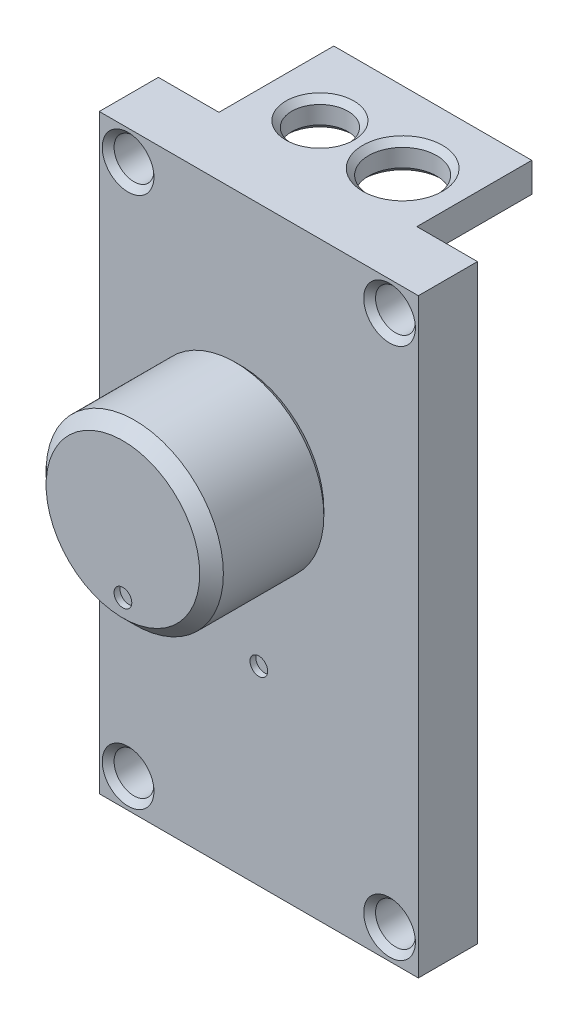
SolidWorks part; units mm, degrees
ref_plane "Front" through (0, 0, 0) normal (0, 0, 1) x (1, 0, 0)
ref_plane "Top" through (0, 0, 0) normal (0, 1, 0) x (1, 0, 0)
ref_plane "Right" through (0, 0, 0) normal (1, 0, 0) x (0, 0, -1)
sketch "Sketch1" plane through (0, 0, 0) normal (0, 0, 1) x (1, 0, 0)
  line L0 (-3.9725, 10.7262) -> (0.1506, 10.7262)
  line L1 (-5.9109, 4.6646) -> (-5.9109, 8.7877)
  line L2 (2.0891, 4.6646) -> (2.0891, 8.7877)
  line L3 (-3.9725, 2.7262) -> (0.1506, 2.7262)
  line L5 (-1.9109, 10.7262) -> (-1.9109, 2.7262) construction
  line L6 (25.0891, 42.9762) -> (25.0891, -57.0238) construction
  line L8 (25.0891, -57.0238) -> (-28.9109, -57.0238) construction
  line L9 (25.0891, 42.9762) -> (25.0891, -57.0238)
  line L10 (25.0891, 42.9762) -> (-28.9109, 42.9762)
  line L11 (25.0891, -57.0238) -> (-28.9109, -57.0238)
  line L12 (-28.9109, 42.9762) -> (-28.9109, -57.0238)
  line L13 (-19.1609, 6.7262) -> (15.3391, 6.7262) construction
  line L14 (-19.1609, 42.9762) -> (-19.1609, -29.5238) construction
  line L15 (15.3391, 42.9762) -> (15.3391, -29.5238) construction
  arc A0 (-3.9725, 10.7262) -> (-5.9109, 8.7877) centre (-1.9109, 6.7262) ccw
  arc A1 (2.0891, 8.7877) -> (0.1506, 10.7262) centre (-1.9109, 6.7262) ccw
  arc A3 (0.1506, 2.7262) -> (2.0891, 4.6646) centre (-1.9109, 6.7262) ccw
  arc A4 (-5.9109, 4.6646) -> (-3.9725, 2.7262) centre (-1.9109, 6.7262) ccw
  dimension "D1" = 9
  dimension "D3" = 8
  dimension "D4" = 8
extrude "Boss-Extrude1" add sketch "Sketch1" along normal blind 10
ref_plane "Plane1" through (0, 0, 13) normal (0, 0, 1) x (1, 0, 0)
sketch "Sketch2" plane through (0, 0, 13) normal (0, 0, 1) x (1, 0, 0)
  line L0 (0.9157, 8.2262) -> (-4.7376, 8.2262)
  arc A0 (-4.7376, 8.2262) -> (0.9157, 8.2262) centre (-1.9109, 6.7262) ccw
  circle A1 centre (-1.9109, 6.7262) radius 15
  point P1 (-1.9109, 3.5262)
  dimension "D1" = 3.2
  dimension "D3" = 30
  dimension "D2" = 4.7
extrude "Boss-Extrude2" add sketch "Sketch2" along normal blind 20 separate body contours A1
extrude "Cut-Extrude1" cut sketch "Sketch2<3>" along normal blind 11 contours L0 A0
sketch "Sketch2<3>" plane through (0, 0, 13) normal (0, 0, 1) x (1, 0, 0) same geometry as "Sketch2"
chamfer "Chamfer1" distance 2 angle 45 1 edges at (13.0891, 6.7262, 33)
sketch "Sketch5" plane through (0, 0, 33) normal (0, 0, 1) x (1, 0, 0)
  line L0 (-1.9109, 6.7262) -> (-1.9109, -3.2738) construction
  circle A1 centre (-1.9109, -3.2738) radius 1.5
  dimension "D1" = 3
  dimension "D2" = 10
extrude "Cut-Extrude2" cut sketch "Sketch5" against normal blind 1 contours A1
chamfer "Chamfer2" distance 1 angle 45 3 edges at (-1.9109, 3.5262, 13) (-1.9109, 8.2262, 13) (13.0891, 6.7262, 13)
sketch "Sketch6" plane through (0, 0, 13) normal (0, 0, -1) x (-1, 0, 0)
  line L0 (-1.464, 9.2262) -> (5.2858, 9.2262) construction
  line L1 (-1.464, 9.2262) -> (5.2858, 9.2262) construction
  line L2 (-1.7071, 9.7262) -> (5.5289, 9.7262)
  circle A0 centre (1.9109, 6.7262) radius 14 construction
  arc A1 (-1.464, 9.2262) -> (5.2858, 9.2262) centre (1.9109, 6.7262) ccw construction
  circle A2 centre (1.9109, 6.7262) radius 14 construction
  arc A3 (-1.464, 9.2262) -> (5.2858, 9.2262) centre (1.9109, 6.7262) ccw construction
  arc A4 (-1.7071, 9.7262) -> (5.5289, 9.7262) centre (1.9109, 6.7262) ccw
  circle A5 centre (1.9109, 6.7262) radius 12.5
  dimension "D1" = 0.5
  dimension "D2" = 1.5
extrude "Cut-Extrude3" cut sketch "Sketch6" against normal blind 15.5
fillet "Fillet1" radius 1 3 edges at (-14.4109, 6.7262, 28.5) (-1.9109, 2.0262, 28.5) (-1.9109, 9.7262, 28.5)
sketch "Sketch7" plane through (0, 0, 10) normal (0, 0, 1) x (1, 0, 0)
  line L0 (-1.9109, -24.8226) -> (-1.9109, 6.7262) construction
  circle A0 centre (-1.9109, -24.8226) radius 1.5
  circle A1 centre (-1.9109, -3.2738) radius 1.5 construction
extrude "Cut-Extrude4" cut sketch "Sketch7" against normal blind 1
sketch "Sketch8" plane through (0, 42.9762, 0) normal (0, 1, 0) x (1, 0, 0)
  line L0 (15.3391, 19.938) -> (-19.1609, 19.938) construction
  line L1 (15.3391, 19.938) -> (15.3391, 0) construction
  line L2 (-19.1609, 19.938) -> (-19.1609, 0) construction
  line L3 (-18.6609, 0.5) -> (-18.6609, 0)
  line L4 (25.0891, 0) -> (-28.9109, 0) construction
  line L5 (14.8391, 19.438) -> (14.8391, 0.5)
  line L6 (-18.6609, 0) -> (14.8391, 0)
  line L7 (-18.6609, 19.438) -> (-18.6609, 0.5)
  line L8 (14.8391, 19.438) -> (-18.6609, 19.438)
  line L9 (14.8391, 0.5) -> (-18.6609, 0.5) construction
  line L10 (15.3391, 0) -> (-19.1609, 0) construction
  line L11 (14.8391, 0) -> (14.8391, 0.5)
  dimension "D1" = 0.5
extrude "Boss-Extrude3" add sketch "Sketch8" against normal blind 5
hole_wizard "CBORE for #4 Binding Head Machine Screw1" positions "Sketch10" profile "Sketch9" counterbore size "#4" standard "ANSI Inch" end condition through all
sketch "Sketch10" plane through (0, 0, 10) normal (0, 0, 1) x (1, 0, 0)
  point P0 (20.2141, -52.0238)
  point P3 (-24.0359, -52.0238)
  point P6 (-24.0359, 37.9762)
  point P9 (20.2141, 37.9762)
sketch "Sketch9" plane through (20.2141, -52.0238, 10) normal (1, 0, 0) x (0, -1, 0)
  line L0 (0, 0) -> (0, 29.438)
  line L1 (0, 29.438) -> (1.6319, 29.438)
  line L3 (1.6319, 29.438) -> (1.632, 7.7272)
  line L4 (1.632, 7.7272) -> (3.3731, 7.7272)
  line L5 (3.3731, 7.7272) -> (3.3731, 0)
  line L7 (3.3731, 0) -> (0, 0)
  line L11 (0, -6.35) -> (0, 107.95) construction
  dimension "Thru Hole Dia." = 3.2639
  dimension "Thru Hole Depth" = 29.438
  dimension "C'Bore Dia." = 6.7462
  dimension "C'Bore Depth" = 7.7272
sketch "Sketch11" plane through (0, 42.9762, 0) normal (0, 1, 0) x (1, 0, 0)
  line L0 (-8.9109, 7.339) -> (5.0891, 7.339) construction
  line L1 (14.8391, 19.438) -> (-18.6609, 19.438) construction
  line L3 (-1.9109, -4.7599) -> (-1.9109, 19.438) construction
  circle A0 centre (5.0891, 7.339) radius 5.75
  circle A1 centre (-8.9109, 7.339) radius 4.75
  point P5 (-1.9109, 7.339)
  dimension "D1" = 9.5
  dimension "D2" = 11.5
  dimension "D3" = 14
extrude "Cut-Extrude5" cut sketch "Sketch11" against normal up to next (5 mm away) contours A1 | A0
chamfer "Chamfer4" distance 1 angle 45 4 edges at (-13.6609, 37.9762, -7.339) (-13.6609, 42.9762, -7.339) (-0.6609, 37.9762, -7.339) (-0.6609, 42.9762, -7.339)
sketch "Sketch12" plane through (0, 0, 0) normal (0, 0, -1) x (-1, 0, 0)
  line L10 (-16.0891, 28.9762) -> (-16.0891, 34.9762)
  line L11 (-16.0891, 34.9762) -> (19.9109, 34.9762)
  line L12 (19.9109, 34.9762) -> (19.9109, 28.9762)
  line L13 (18.6609, 37.9762) -> (-14.8391, 37.9762) construction
  line L20 (19.9109, 28.9762) -> (-16.0891, 28.9762)
  line L21 (-16.0891, 28.9762) -> (-16.0891, -48.0238)
  line L22 (-16.0891, -48.0238) -> (19.9109, -48.0238)
  line L23 (19.9109, -48.0238) -> (19.9109, 28.9762)
  line L25 (-16.0891, 28.9762) -> (-16.0891, -48.0238)
  line L26 (-16.0891, -48.0238) -> (19.9109, -48.0238)
  line L27 (19.9109, -48.0238) -> (19.9109, 28.9762)
  dimension "D2" = 3
  dimension "D1" = 9
extrude "Cut-Extrude6" cut sketch "Sketch12" against normal offset from surface (8.5 mm away) 1.5 up to face at (23.5872, -52.0238, 10)
chamfer "Chamfer6" distance 1 angle 45 4 edges at (-20.6628, -52.0238, 10) (23.5872, -52.0238, 10) (23.5872, 37.9762, 10) (-20.6628, 37.9762, 10)
sketch "Sketch13" plane through (0, 0, 13) normal (0, 0, -1) x (-1, 0, 0)
  line L0 (-3.7551, 9.7262) -> (8.0393, 9.7262)
  line L1 (-3.7551, 9.7262) -> (-3.7551, 0.0297)
  line L2 (8.0393, 9.7262) -> (8.0393, 0.0297)
  line L3 (-3.7551, 0.0297) -> (8.0393, 0.0297)
  line L4 (5.5289, 9.7262) -> (-1.7071, 9.7262) construction
extrude "Cut-Extrude7" cut sketch "Sketch13" against normal blind 3
chamfer "Chamfer7" distance 0.5 angle 45 2 edges at (-1.9109, 3.5262, 16) (-1.9109, 8.2262, 16)
sketch "Sketch14" plane through (0, 0, 16) normal (0, 0, -1) x (-1, 0, 0)
  line L0 (1.4109, 12.5365) -> (1.4109, -0.4568)
  line L1 (1.4109, 12.5365) -> (2.4109, 12.5365)
  line L2 (1.4109, -0.4568) -> (2.4109, -0.4568)
  line L3 (2.4109, 12.5365) -> (2.4109, -0.4568)
  line L4 (1.9109, 9.7262) -> (1.9109, 12.5365) construction
  line L5 (5.5289, 9.7262) -> (-1.7071, 9.7262) construction
  dimension "D1" = 1
extrude "Cut-Extrude8" cut sketch "Sketch14" against normal blind 7
